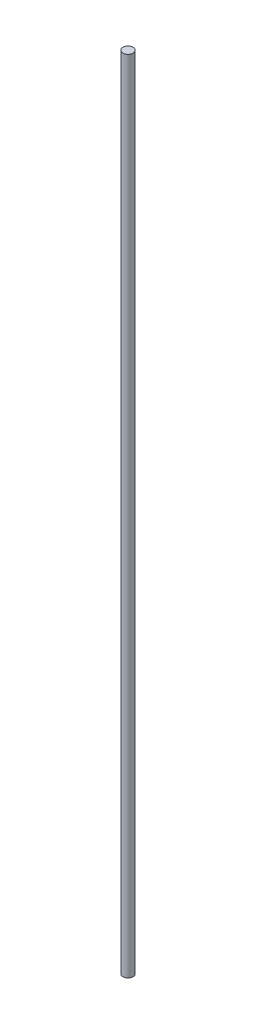
SolidWorks part; units mm, degrees
material "AISI 1020"
ref_plane "Front Plane" through (0, 0, 0) normal (0, 0, 1) x (1, 0, 0)
ref_plane "Top Plane" through (0, 0, 0) normal (0, 1, 0) x (1, 0, 0)
ref_plane "Right Plane" through (0, 0, 0) normal (1, 0, 0) x (0, 0, -1)
sketch "Sketch1" plane through (0, 0, 0) normal (0, 1, 0) x (1, 0, 0)
  circle A0 centre (0, 0) radius 2.5
  dimension "D1" = 5
extrude "Boss-Extrude1" add sketch "Sketch1" along normal blind 195 and the other way blind 195
cosmetic thread "Cosmetic Thread1"
